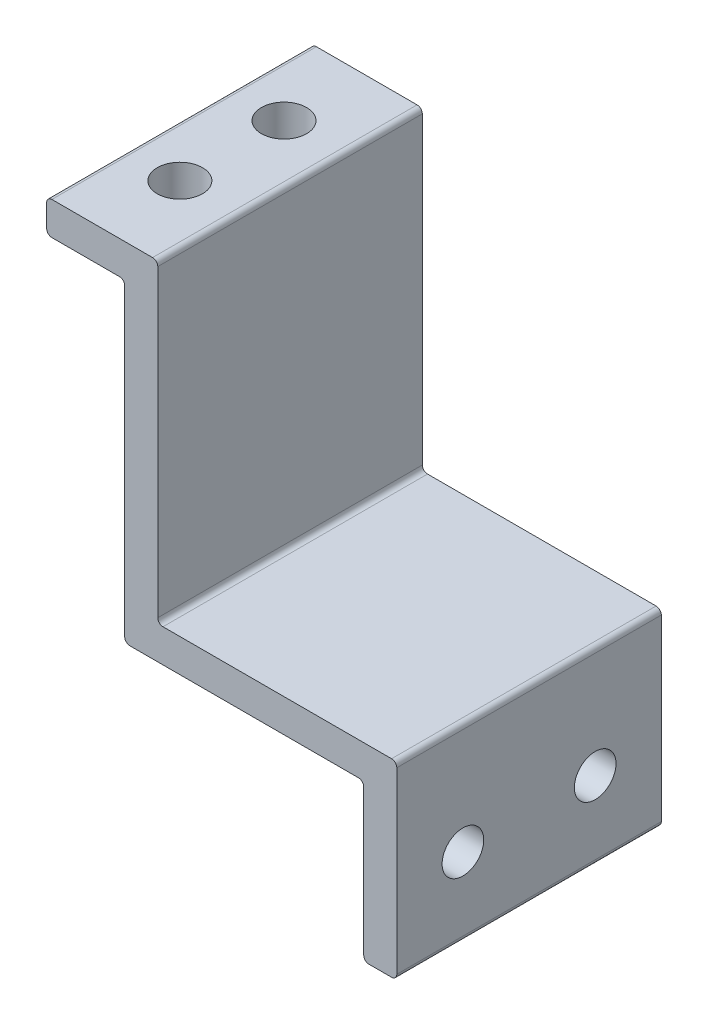
SolidWorks part; units mm, degrees
material "PLA"
ref_plane "Front Plane" through (0, 0, 0) normal (0, 0, 1) x (1, 0, 0)
ref_plane "Top Plane" through (0, 0, 0) normal (0, 1, 0) x (1, 0, 0)
ref_plane "Right Plane" through (0, 0, 0) normal (1, 0, 0) x (0, 0, -1)
sketch "Sketch1" plane through (0, 0, 0) normal (0, 0, 1) x (1, 0, 0)
  line L0 (-96.8188, 43.5162) -> (-96.8188, 40.3412)
  line L1 (-96.8188, 40.3412) -> (-89.3258, 40.3412)
  line L2 (-89.3258, 40.3412) -> (-89.3258, 10.1412)
  line L3 (-89.3258, 10.1412) -> (-66.3758, 10.1412)
  line L4 (-66.3758, 10.1412) -> (-66.3758, -4.8588)
  line L5 (-66.3758, -4.8588) -> (-63.2008, -4.8588)
  line L6 (-63.2008, -4.8588) -> (-63.2008, 13.3162)
  line L7 (-63.2008, 13.3162) -> (-86.1508, 13.3162)
  line L8 (-86.1508, 13.3162) -> (-86.1508, 43.5162)
  line L9 (-86.1508, 43.5162) -> (-96.8188, 43.5162)
  dimension "D1" = 22.95
  dimension "D2" = 3.175
  dimension "D3" = 3.175
  dimension "D4" = 3.175
  dimension "D5" = 30.2
  dimension "D6" = 10.668
  dimension "D7" = 7.493
  dimension "D8" = 3.175
  dimension "D9" = 18.175
extrude "Boss-Extrude1" add sketch "Sketch1" along normal blind 25.4
sketch "Sketch2" plane through (-66.3758, 0, 0) normal (-1, 0, 0) x (0, 0, 1)
  line L0 (12.7, 10.1412) -> (12.7, -4.8588) construction
  line L1 (25.4, 10.1412) -> (0, 10.1412) construction
  line L2 (25.4, -4.8588) -> (0, -4.8588) construction
  line L3 (0, 10.1412) -> (0, -4.8588) construction
  circle A0 centre (6.35, 2.6412) radius 2
  circle A1 centre (19.05, 2.6412) radius 2
  dimension "D1" = 4
  dimension "D3" = 6.35
  dimension "D4" = 7.5
extrude "Cut-Extrude1" cut sketch "Sketch2" against normal through all
fillet "Fillet1" radius 0.5 9 edges at (-86.1508, 43.5162, 12.7) (-86.1508, 13.3162, 12.7) (-63.2008, -4.8588, 12.7) (-63.2008, 13.3162, 12.7) (-66.3758, 10.1412, 12.7) (-66.3758, -4.8588, 12.7) (-89.3258, 10.1412, 12.7) (-96.8188, 43.5162, 12.7) (-96.8188, 40.3412, 12.7)
sketch "Sketch3" plane through (0, 43.5162, 0) normal (0, 1, 0) x (1, 0, 0)
  line L2 (-86.6508, -25.4) -> (-86.6508, 0) construction
  line L3 (-86.6508, 0) -> (-96.3188, 0) construction
  circle A0 centre (-91.7308, -7.7) radius 2.175
  circle A1 centre (-91.7308, -17.7) radius 2.175
  dimension "D1" = 4.35
  dimension "D2" = 4.35
  dimension "D3" = 10
  dimension "D4" = 7.7
  dimension "D5" = 5.08
extrude "Cut-Extrude2" cut sketch "Sketch3" against normal blind 6.604
sketch "Sketch4" plane through (0, 40.3412, 0) normal (0, -1, 0) x (-1, 0, 0)
  circle A0 centre (91.7308, -17.7) radius 4.25
  circle A1 centre (91.7308, -7.7) radius 4.25
  dimension "D1" = 8.5
  dimension "D2" = 8.5
extrude "Cut-Extrude3" cut sketch "Sketch4" along normal blind 5.842
fillet "Fillet2" radius 0.5 13 edges at (-89.3258, 37.4202, 21.2041) (-89.3258, 34.4992, 17.7) (-87.4808, 34.4992, 17.7) (-89.3258, 37.4202, 14.1959) (-89.3258, 37.4202, 11.2041) (-89.3258, 34.4992, 7.7) (-87.4808, 34.4992, 7.7) (-89.3258, 37.4202, 4.1959) (-87.4808, 40.3412, 7.7) (-87.4808, 40.3412, 17.7) (-89.3258, 40.3412, 23.302) (-89.3258, 40.3412, 2.098) (-89.3258, 40.3412, 12.7)
